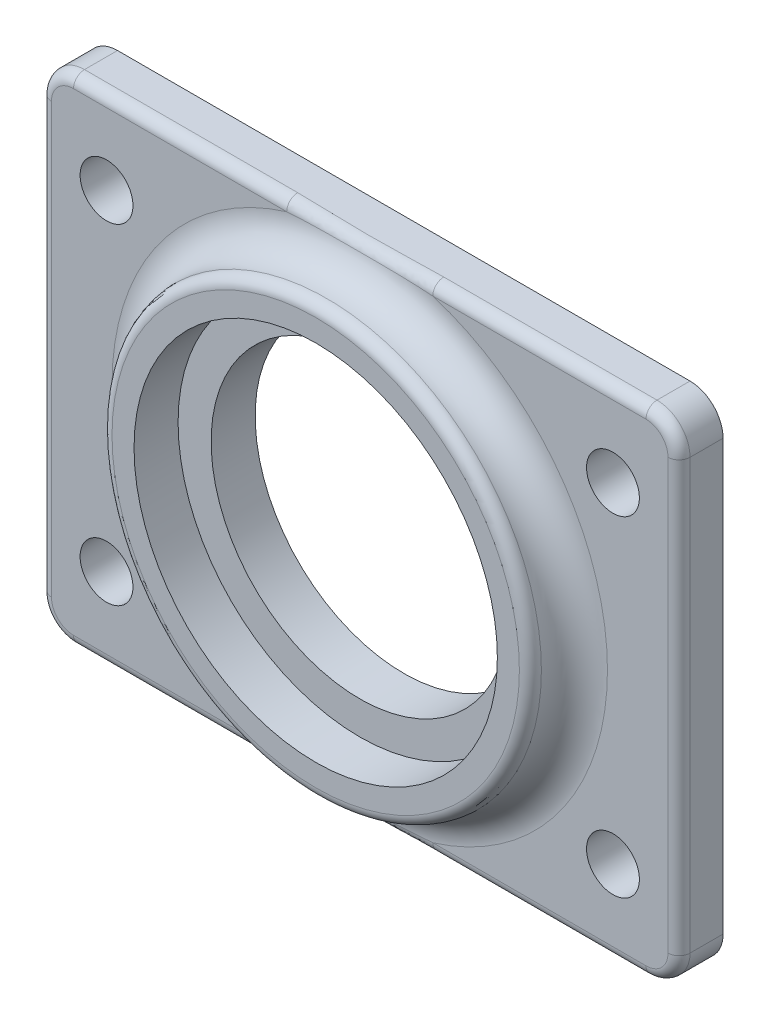
SolidWorks part; units mm, degrees
material "ABS"
ref_plane "X-Y Datum" through (0, 0, 0) normal (0, 0, 1) x (1, 0, 0)
ref_plane "X-Z Datum" through (0, 0, 0) normal (0, 1, 0) x (1, 0, 0)
ref_plane "Y-Z Datum" through (0, 0, 0) normal (1, 0, 0) x (0, 0, -1)
sketch "Sketch1" plane through (0, 0, 0) normal (0, 0, 1) x (1, 0, 0)
  line L1 (-29, 22.5) -> (29, 22.5)
  line L2 (-29, 22.5) -> (-29, -22.5)
  line L3 (-29, -22.5) -> (29, -22.5)
  line L4 (29, 22.5) -> (29, -22.5)
  line L5 (-29, 22.5) -> (29, -22.5) construction
  line L6 (-29, -22.5) -> (29, 22.5) construction
  line L7 (-23, 15) -> (23, 15) construction
  line L8 (-23, 15) -> (-23, -15) construction
  line L9 (-23, -15) -> (23, -15) construction
  line L10 (23, 15) -> (23, -15) construction
  line L11 (-23, 15) -> (23, -15) construction
  line L12 (-23, -15) -> (23, 15) construction
  circle A0 centre (0, 0) radius 16.5 construction
  circle A1 centre (-23, 15) radius 2
  circle A2 centre (-23, -15) radius 2
  circle A3 centre (23, -15) radius 2
  circle A4 centre (23, 15) radius 2
  dimension "D1" = 33
  dimension "D4" = 4
  dimension "D2" = 58
  dimension "D3" = 45
  dimension "D5" = 30
  dimension "D6" = 46
extrude "Boss-Extrude1" add sketch "Sketch1" along normal blind 4 contours L4 L1 L2 L3 A4 A3 A2 A1 | A1 | A2 | A3 | A4 region at (0, 0, 0) region at (-23, 15, 0) region at (-23, -15, 0) region at (23, -15, 0) region at (23, 15, 0)
sketch "Sketch4" plane through (0, 0, 4) normal (0, 0, 1) x (1, 0, 0)
  circle A0 centre (0, 0) radius 16.5
  circle A1 centre (0, 0) radius 19.5
  dimension "D1" = 33
  dimension "D2" = 3
extrude "Boss-Extrude3" add sketch "Sketch4" along normal blind 4
sketch "Sketch5" plane through (0, 0, 4) normal (0, 0, 1) x (1, 0, 0)
  circle A0 centre (0, 0) radius 13.5
  dimension "D1" = 27
extrude "Cut-Extrude2" cut sketch "Sketch5" against normal through all
hole_wizard "M4 Clearance Hole1" positions "Sketch8" profile "Sketch7" hole size "M4" standard "ANSI Metric" end condition through all
sketch "Sketch8" plane through (0, 0, 4) normal (0, 0, 1) x (1, 0, 0)
  point P0 (23, 15)
  point P3 (23, -15)
  point P6 (-23, -15)
  point P9 (-23, 15)
sketch "Sketch7" plane through (23, 15, 4) normal (1, 0, 0) x (0, -1, 0)
  line L0 (0, 0) -> (0, 4)
  line L1 (0, 4) -> (2.4, 4)
  line L2 (2.4, 4) -> (2.4, 0)
  line L5 (2.4, 0) -> (0, 0)
  line L11 (0, -6.35) -> (0, 107.95) construction
  dimension "Thru Hole Dia." = 4.8
  dimension "Thru Hole Depth" = 4
fillet "Fillet1" radius 3 5 edges at (-29, -22.5, 2) (-29, 22.5, 2) (19.5, 0, 4) (29, -22.5, 2) (29, 22.5, 2)
fillet "Fillet2" radius 1 11 edges at (28.1213, 21.6213, 4) (13, 22.5, 4) (-13, 22.5, 4) (-28.1213, 21.6213, 4) (-29, 0, 4) (-28.1213, -21.6213, 4) (-13, -22.5, 4) (13, -22.5, 4) (28.1213, -21.6213, 4) (19.5, 0, 8) (29, 0, 4)
